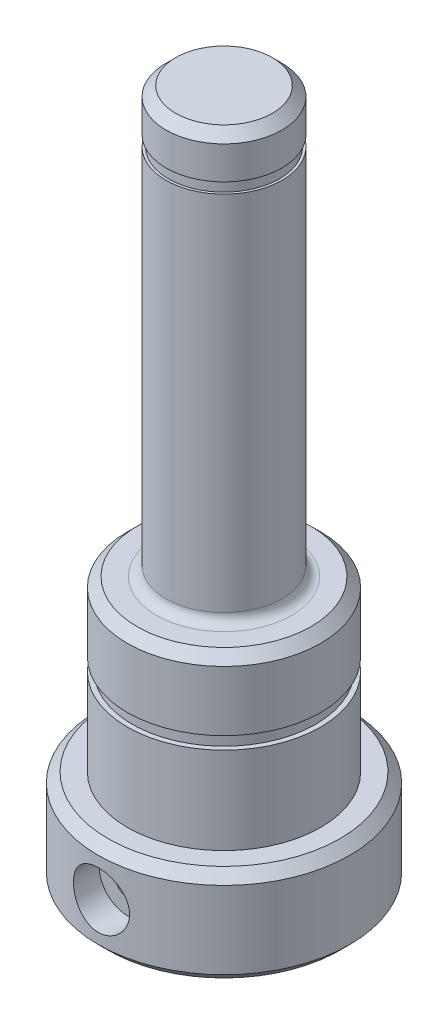
SolidWorks part; units mm, degrees
ref_plane "Front Plane" through (0, 0, 0) normal (0, 0, 1) x (1, 0, 0)
ref_plane "Top Plane" through (0, 0, 0) normal (0, 1, 0) x (1, 0, 0)
ref_plane "Right Plane" through (0, 0, 0) normal (1, 0, 0) x (0, 0, -1)
ref_axis "X" through (88.99, 0, 0) along (-1, 0, 0)
ref_axis "Y" through (0, 55, 0) along (0, -1, 0)
ref_axis "Z" through (0, 0, -88.99) along (0, 0, 1)
sketch "Sketch1" plane through (0, 0, 0) normal (0, 0, 1) x (1, 0, 0)
  line L0 (0, 0) -> (-13, 0) construction
  line L1 (0, 0) -> (0, 71.5) construction
  line L2 (0, 0) -> (-13, 0)
  line L3 (-10, 10) -> (-10, 19)
  line L4 (-10, 27.5) -> (-6, 27.5)
  line L5 (-6, 27.5) -> (-6, 66)
  line L6 (-6, 71.5) -> (0, 71.5)
  line L7 (0, 71.5) -> (0, 0)
  line L10 (-13, 0) -> (-13, 10)
  line L11 (-13, 10) -> (-10, 10)
  line L12 (-10, 27.5) -> (-10, 20.3)
  line L13 (-10, 19) -> (-9.5, 19)
  line L15 (-10, 20.3) -> (-9.5, 20.3)
  line L16 (-9.5, 19) -> (-9.5, 20.3)
  line L17 (-6, 67.1) -> (-6, 71.5)
  line L18 (-6, 66) -> (-5.75, 66)
  line L20 (-6, 67.1) -> (-5.75, 67.1)
  line L21 (-5.75, 66) -> (-5.75, 67.1)
  point P12 (0, 0)
  dimension "D1" = 12
  dimension "D2" = 20
  dimension "D5" = 27.5
  dimension "D6" = 71.5
  dimension "D7" = 10
  dimension "D8" = 26
  dimension "D9" = 9
  dimension "D10" = 1.3
  dimension "D11" = 9.5
  dimension "D12" = 10
  dimension "D13" = 38.5
  dimension "D14" = 1.1
  dimension "D15" = 5.75
revolve "Revolve1" add sketch "Sketch1" angle 360 about L1
fillet "Fillet2" radius 1 1 edges at (6, 27.5, 0)
chamfer "Chamfer1" distance 1 angle 45 4 edges at (10, 27.5, 0) (6, 71.5, 0) (13, 0, 0) (13, 10, 0)
sketch "Sketch2" [suppressed] plane through (0, 0, 0) normal (0, -1, 0) x (1, 0, 0)
  circle A1 centre (0, 0) radius 3.0956
  point P3 (0, 0)
  point P5 (0, 0)
sketch "Sketch5" plane through (0, 0, 0) normal (0, -1, 0) x (1, 0, 0)
  circle A0 centre (0, 0) radius 5.05
  dimension "D1" = 10.1
extrude "Cut-Extrude4" cut sketch "Sketch5" against normal blind 20
ref_plane "Plane1" through (0, 0, 13) normal (0, 0, 1) x (1, 0, 0)
sketch "Sketch3" plane through (0, 0, 13) normal (0, 0, 1) x (1, 0, 0)
  line L0 (-13, 1) -> (13, 1) construction
  line L1 (0, 55) -> (0, -55) construction
  circle A0 centre (0, 5) radius 2.9
  point P0 (0, 5)
  dimension "D2" = 5.8
  dimension "D1" = 4
extrude "Cut-Extrude3" cut sketch "Sketch3" against normal blind 3
sketch "Sketch6" plane through (0, 0, 10) normal (0, 0, 1) x (1, 0, 0)
  point P0 (0, 5)
  point P1 (0, 0)
hole_wizard "Tap Drill for M3 Tap1" positions "3DSketch2" profile "Sketch8" hole size "M3" standard "DIN"
sketch3d "3DSketch2"
  point P0 (0, 5, 13)
  point P3 (0, 5, 13)
  point P5 (0, 5, 10)
sketch "Sketch8" plane through (0, 5, 10) normal (1, 0, 0) x (0, -1, 0)
  line L0 (0, 0) -> (0, 8.7511)
  line L1 (0, 8.7511) -> (1.25, 8)
  line L2 (1.25, 8) -> (1.25, 0)
  line L5 (1.25, 0) -> (0, 0)
  line L10 (0, 8.7511) -> (-1.25, 8) construction
  line L11 (0, -6.35) -> (0, 107.95) construction
  dimension "Hole Dia." = 2.5
  dimension "Hole Depth" = 8
  dimension "Drill Angle" = 118
